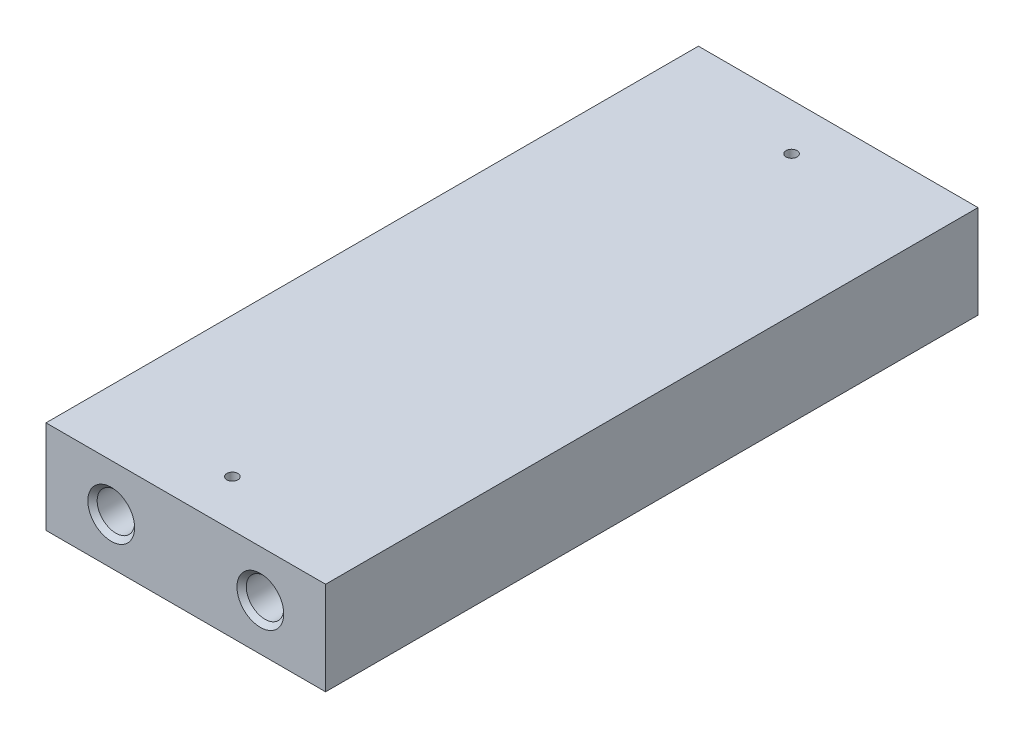
SolidWorks part; units mm, degrees
material "6063-T5"
ref_plane "Front Plane" through (0, 0, 0) normal (0, 0, 1) x (1, 0, 0)
ref_plane "Top Plane" through (0, 0, 0) normal (0, 1, 0) x (1, 0, 0)
ref_plane "Right Plane" through (0, 0, 0) normal (1, 0, 0) x (0, 0, -1)
sketch "Sketch1" plane through (0, 0, 0) normal (0, 0, 1) x (1, 0, 0)
  line L1 (-19.05, -6.35) -> (19.05, -6.35)
  line L2 (-19.05, -6.35) -> (-19.05, 6.35)
  line L3 (-19.05, 6.35) -> (19.05, 6.35)
  line L4 (19.05, -6.35) -> (19.05, 6.35)
  line L5 (-19.05, -6.35) -> (19.05, 6.35) construction
  line L6 (-19.05, 6.35) -> (19.05, -6.35) construction
  point P0 (0, 0)
  dimension "D1" = 38.1
  dimension "D2" = 12.7
extrude "Boss-Extrude1" add sketch "Sketch1" against normal blind 88.9
sketch "Sketch2" plane through (0, 0, 0) normal (0, 0, 1) x (1, 0, 0)
  line L1 (0, -1000) -> (0, 49000) construction
  point P0 (-10.16, 0)
  point P1 (10.16, 0)
  dimension "D1" = 20.32
hole_wizard "1/4-20 Tapped Hole1" positions "3DSketch1" profile "Sketch4" tap size "1/4-20" standard "ANSI Inch"
sketch3d "3DSketch1"
  point P0 (-10.16, 0, 0)
  point P3 (10.16, 0, 0)
sketch "Sketch4" plane through (-10.16, 0, 0) normal (1, 0, 0) x (0, -1, 0)
  line L0 (0, 0) -> (0, 14.2338)
  line L1 (0, 14.2338) -> (2.5527, 12.7)
  line L2 (2.5527, 12.7) -> (2.5527, 0.635)
  line L3 (2.5527, 0.635) -> (3.1877, 0)
  line L5 (3.1877, 0) -> (0, 0)
  line L6 (-2.5527, 0.635) -> (-3.1877, 0) construction
  line L10 (0, 14.2338) -> (-2.5527, 12.7) construction
  line L11 (0, -6.35) -> (0, 107.95) construction
  dimension "Tap Drill Dia." = 5.1054
  dimension "Tap Drill Depth" = 12.7
  dimension "Near C'Sink Dia." = 6.3754
  dimension "Near C'Sink Angle" = 90
  dimension "Drill Angle" = 118
cosmetic thread "Hole Thread1" parameters "D1"=10.16, "D2"=6.35
cosmetic thread "Hole Thread2" parameters "D1"=10.16, "D2"=6.35
ref_plane "Plane1" through (0, 0, -44.45) normal (0, 0, 1) x (1, 0, 0)
mirror "Mirror1" about plane through (0, 0, -44.45) normal (0, 0, 1) of "1/4-20 Tapped Hole1"
sketch "Sketch5" plane through (0, 6.35, 0) normal (0, 1, 0) x (1, 0, 0)
  line L0 (0, -1000) -> (0, 49000) construction
  line L1 (-999.1252, 44.45) -> (49000.8748, 44.45) construction
  line L3 (19.05, 0) -> (-19.05, 0) construction
  line L4 (19.05, 88.9) -> (-19.05, 88.9) construction
  point P4 (0, 82.55)
  point P6 (0, 6.35)
  dimension "D1" = 76.2
hole_wizard "#1-64 Tapped Hole1" positions "3DSketch2" profile "Sketch7" tap size "#1-64" standard "ANSI Inch" end condition through all
sketch3d "3DSketch2"
  point P0 (0, 6.35, -82.55)
  point P3 (0, 6.35, -6.35)
sketch "Sketch7" plane through (0, 6.35, -82.55) normal (1, 0, 0) x (0, 0, 1)
  line L0 (0, 0) -> (0, 12.7)
  line L1 (0, 12.7) -> (0.7556, 12.7)
  line L2 (0.7556, 12.7) -> (0.7556, 0)
  line L5 (0.7556, 0) -> (0, 0)
  line L11 (0, -6.35) -> (0, 107.95) construction
  dimension "Thru Tap Drill Dia." = 1.5113
  dimension "Thru Tap Drill Depth" = 12.7
cosmetic thread "Hole Thread3" parameters "D2"=1.8542
cosmetic thread "Hole Thread4" parameters "D2"=1.8542
sketch "Sketch11" plane through (-19.05, 0, 0) normal (-1, 0, 0) x (0, 0, 1)
  line L0 (-1048.0986, 0) -> (48951.9014, 0) construction
  line L1 (-44.45, -1002.8477) -> (-44.45, 48997.1523) construction
  line L2 (-44.45, -6.985) -> (-44.45, 6.985) construction
  line L3 (201000, 6.35) -> (-249000, 6.35) construction
  line L4 (-88.9, -6.35) -> (0, -6.35) construction
  point P10 (-69.85, 0)
  point P11 (-19.05, 0)
  dimension "D1" = 50.8
hole_wizard "1/4-20 Tapped Hole3" positions "Sketch12" profile "Sketch13" tap size "1/4-20" standard "ANSI Inch"
sketch "Sketch12" plane through (-19.05, 0, 0) normal (-1, 0, 0) x (0, 0, 1)
  point P0 (-69.85, 0)
  point P3 (-19.05, 0)
sketch "Sketch13" plane through (-19.05, 0, -69.85) normal (0, 1, 0) x (0, 0, 1)
  line L0 (0, 0) -> (0, 15.5038)
  line L1 (0, 15.5038) -> (2.5527, 13.97)
  line L2 (2.5527, 13.97) -> (2.5527, 0.635)
  line L3 (2.5527, 0.635) -> (3.1877, 0)
  line L5 (3.1877, 0) -> (0, 0)
  line L6 (-2.5527, 0.635) -> (-3.1877, 0) construction
  line L10 (0, 15.5038) -> (-2.5527, 13.97) construction
  line L11 (0, -6.35) -> (0, 107.95) construction
  dimension "Tap Drill Dia." = 5.1054
  dimension "Tap Drill Depth" = 13.97
  dimension "Near C'Sink Dia." = 6.3754
  dimension "Near C'Sink Angle" = 90
  dimension "Drill Angle" = 118
cosmetic thread "Hole Thread7" parameters "D1"=10.16, "D2"=6.35
cosmetic thread "Hole Thread8" parameters "D1"=10.16, "D2"=6.35
